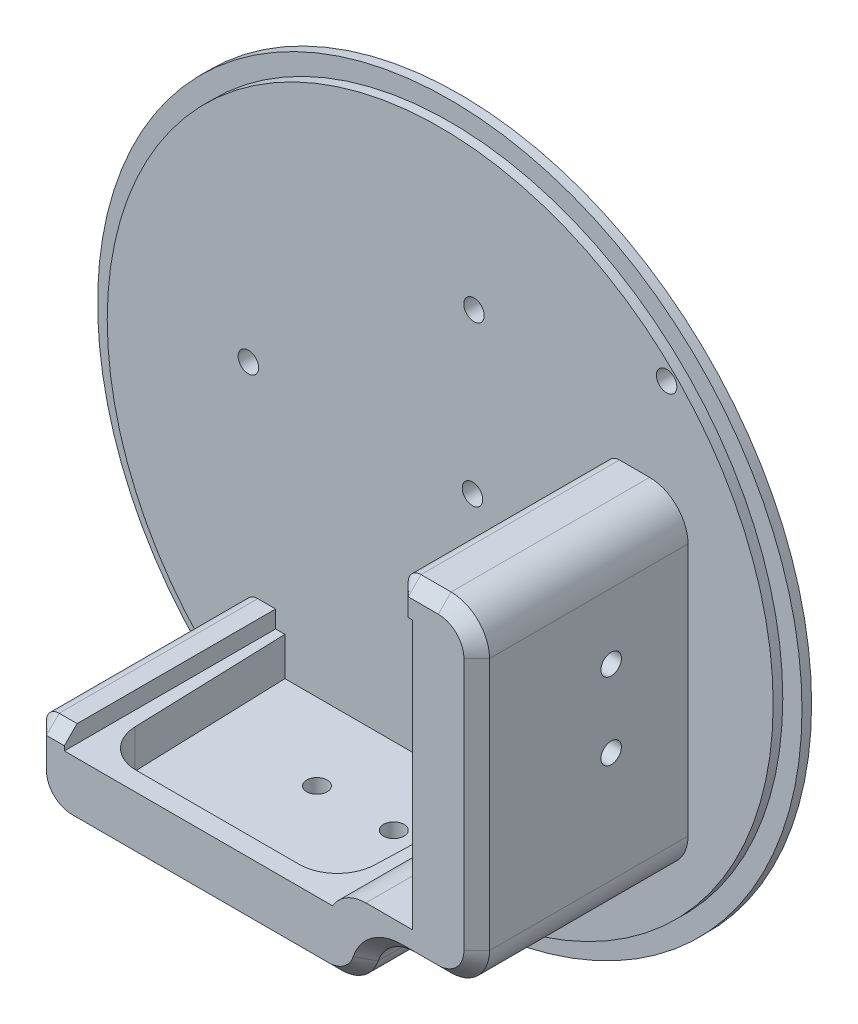
SolidWorks part; units mm, degrees
material "ABS"
ref_plane "Ebene vorne" through (0, 0, 0) normal (0, 0, 1) x (1, 0, 0)
ref_plane "Ebene oben" through (0, 0, 0) normal (0, 1, 0) x (1, 0, 0)
ref_plane "Ebene rechts" through (0, 0, 0) normal (1, 0, 0) x (0, 0, -1)
sketch "Skizze1" plane through (0, 0, 0) normal (0, 0, 1) x (1, 0, 0)
  circle A0 centre (0, 0) radius 55
  circle A1 centre (0, 0) radius 52
  point P15 (0, 0)
  point P23 (0, 0)
  dimension "D1" = 110
  dimension "D2" = 3
extrude "Aufsatz-Linear austragen1" add sketch "Skizze1" along normal blind 3 contours A1 region at (0, 0, 0)
extrude "Aufsatz-Linear austragen2" add sketch "Skizze1<3>" along normal blind 1.5 contours A0 A1 region at (-53.4444, 0, 0)
sketch "Skizze1<3>" plane through (0, 0, 0) normal (0, 0, 1) x (1, 0, 0) same geometry as "Skizze1"
sketch "Skizze2" plane through (0, 0, 3) normal (0, 0, 1) x (1, 0, 0)
  line L0 (25.9967, -4.75) -> (33.2967, -4.75) construction
  line L1 (26, 21) -> (26, 16.2)
  line L2 (26, 16.2) -> (27.2, 16.2)
  line L3 (26, 21) -> (33.3, 21)
  line L4 (26, -25.7) -> (16.2, -25.7)
  line L5 (27.2, -25.7) -> (26, -25.7)
  line L6 (27.2, 16.2) -> (28.7, 16.2)
  line L7 (28.7, 16.2) -> (28.7, 15)
  line L8 (16.2, -25.7) -> (16.2, -26)
  line L10 (28.7, -25.7) -> (28.7, -24.5)
  line L11 (27.2, -25.7) -> (28.7, -25.7)
  line L14 (26, -30.5) -> (33.3, -30.5)
  line L15 (16.2, -27.2) -> (16.2, -26)
  line L17 (-25.7, -27.2) -> (-25.7, -26)
  line L18 (-25.7, -26) -> (-30.5, -26)
  line L19 (21, -30.5) -> (21, -33.3)
  line L22 (16.2, -27.2) -> (16.2, -28.7)
  line L23 (16.2, -28.7) -> (15, -28.7)
  line L25 (38.7, 15) -> (38.7, 21)
  line L26 (-25.7, -28.7) -> (-24.5, -28.7)
  line L27 (-25.7, -27.2) -> (-25.7, -28.7)
  line L28 (15, -28.7) -> (-24.5, -28.7)
  line L30 (-30.5, -26) -> (-30.5, -33.3)
  line L31 (38.7, 21) -> (33.3, 21)
  line L32 (15, -38.7) -> (-24.5, -38.7)
  line L33 (-4.75, -25.9967) -> (-4.75, -33.2967) construction
  line L34 (26, -30.5) -> (21, -30.5)
  line L36 (38.7, -24.5) -> (38.7, -30.5)
  line L37 (38.7, -30.5) -> (33.3, -30.5)
  line L38 (28.7, -24.5) -> (28.7, 15)
  line L39 (21, -33.3) -> (21, -38.7)
  line L40 (38.7, -24.5) -> (38.7, 15)
  line L41 (21, -26) -> (21, -33.3) [skipped]
  line L42 (21, -38.7) -> (15, -38.7)
  line L43 (-30.5, -33.3) -> (-30.5, -38.7)
  line L44 (-30.5, -38.7) -> (-24.5, -38.7)
  point P1 (0, 0)
  point P41 (0, 0)
  dimension "D6" = 2
  dimension "D10" = 10
sketch "Skizze3" plane through (0, 0, 3) normal (0, 0, 1) x (1, 0, 0)
  circle A0 centre (5.0416, 4.9489) radius 1.6
  circle A1 centre (5.2758, 29.9478) radius 1.6
  circle A2 centre (-29.9569, 5.2768) radius 1.6
  dimension "D1" = 3.2
  dimension "D2" = 3.2
  dimension "D3" = 3.2
extrude "Schnitt-Linear austragen1" cut sketch "Skizze3" against normal up to next
extrude "Aufsatz-Linear austragen3" add sketch "Skizze2" along normal blind 33 contours L3 L31 L25 L40 L36 L37 L14 L34 L19 L39 L42 L32 L44 L43 L30 L18 L17 L27 L26 L28 L23 L22 L15 L8 L4 L5 L11 L10 L38 L7 L6 L2 L1
sketch "Skizze6" plane through (0, -38.7, 0) normal (0, -1, 0) x (1, 0, 0)
  line L0 (-4.75, 36) -> (-4.75, 3) construction
  line L1 (21, 36) -> (-30.5, 36) construction
  line L2 (21, 3) -> (-30.5, 3) construction
  line L3 (-24.25, 3) -> (-23.25, 33)
  line L4 (-23.25, 33) -> (13.75, 33)
  line L5 (-24.25, 3) -> (14.75, 3)
  line L6 (14.75, 3) -> (13.75, 33)
  point P11 (-4.75, 33)
  point P12 (-4.75, 33)
  dimension "D1" = 19.5
  dimension "D2" = 18.5
  dimension "D3" = 30
extrude "Schnitt-Linear austragen4" cut sketch "Skizze6" against normal up to next from offset 4 contours L3 L4 L6 L5 offset against normal yes
fillet "Verrundung1" radius 6 2 edges at (-23.25, -31.7, 33) (13.75, -31.7, 33)
sketch "Skizze7" plane through (28.7, 0, 0) normal (-1, 0, 0) x (0, 0, 1)
  line L0 (36, -4.75) -> (3, -4.75) construction
  line L1 (36, -25.7) -> (36, 16.2) construction
  line L2 (3, 16.2) -> (3, -25.7) construction
  line L3 (33, -23.25) -> (33, 13.75)
  line L4 (3, -24.25) -> (3, 14.75)
  line L5 (33, 13.75) -> (3, 14.75)
  line L6 (33, -23.25) -> (3, -24.25)
  point P11 (33, -4.75)
  dimension "D1" = 18.5
  dimension "D2" = 19.5
  dimension "D3" = 30
extrude "Schnitt-Linear austragen9" cut sketch "Skizze7" against normal blind 6 contours L3 L5 L4 L6
fillet "Verrundung2" radius 6 2 edges at (31.7, -23.25, 33) (31.7, 13.75, 33)
fillet "Verrundung4" radius 6 1 edges at (21, -30.5, 19.5)
fillet "Verrundung5" radius 6 1 edges at (16.2, -25.7, 19.5)
fillet "Verrundung6" radius 2 2 edges at (-30.5, -26, 19.5) (26, 21, 19.5)
sketch "Skizze8" plane through (0, -38.7, 0) normal (0, -1, 0) x (1, 0, 0)
  line L0 (-7.25, 15) -> (4.75, 15) construction
  line L1 (21, 3) -> (-30.5, 3) construction
  line L2 (-30.5, 36) -> (-30.5, 3) construction
  circle A0 centre (4.75, 15) radius 1.6
  circle A1 centre (-7.25, 15) radius 1.6
  dimension "D1" = 3.2
  dimension "D2" = 3.2
  dimension "D3" = 12
  dimension "D4" = 12
  dimension "D5" = 23.25
sketch "Skizze9" plane through (38.7, 0, 0) normal (1, 0, 0) x (0, 0, -1)
  line L0 (-15, -7.25) -> (-15, 4.75) construction
  line L1 (-36, -30.5) -> (-3, -30.5) construction
  line L2 (-3, -30.5) -> (-3, 21) construction
  circle A0 centre (-15, -7.25) radius 1.6
  circle A1 centre (-15, 4.75) radius 1.6
  dimension "D1" = 3.2
  dimension "D2" = 3.2
  dimension "D3" = 12
  dimension "D4" = 23.25
  dimension "D5" = 12
extrude "Schnitt-Linear austragen10" cut sketch "Skizze8" against normal up to next
extrude "Schnitt-Linear austragen11" cut sketch "Skizze9" against normal up to next
fillet "Verrundung7" radius 6 4 edges at (38.7, 21, 19.5) (-30.5, -38.7, 19.5) (21, -38.7, 19.5) (38.7, -30.5, 19.5)
sketch "Skizze10" plane through (0, 0, 0) normal (0, 0, -1) x (-1, 0, 0)
  line L0 (0, 0) -> (55, 0) construction
  line L1 (0, 0) -> (35.3553, -35.3553) construction
  circle A0 centre (35.3553, -35.3553) radius 1.6
  circle A1 centre (-35.3553, 35.3553) radius 1.6
  circle A2 centre (0, 0) radius 55 construction
  point P11 (0, 0)
  point P12 (0, 0)
  dimension "D1" = 3.2
  dimension "D2" = 50
  dimension "D3" = 45
  dimension "D4" = 2
extrude "Schnitt-Linear austragen13" cut sketch "Skizze10" against normal up to next contours A0 | A1
chamfer "Fase1" distance 2 angle 45 14 edges at (-27.1, -26, 36) (-29.9142, -26.5858, 36) (-30.5, -30.35, 36) (-28.7426, -36.9426, 36) (-4.4412, -38.7, 36) (19.1247, -37.5683, 36) (23.4929, -31.6317, 36) (29.85, -30.5, 36) (26, 17.6, 36) (36.9426, -28.7426, 36) (26.5858, 20.4142, 36) (38.7, -4.75, 36) (30.35, 21, 36) (36.9426, 19.2426, 36)
